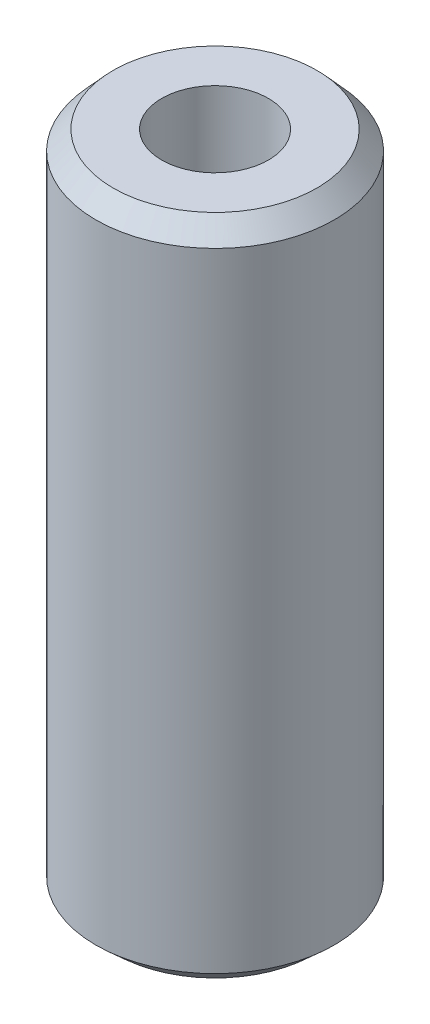
SolidWorks part; units mm, degrees
ref_plane "Front Plane" through (0, 0, 0) normal (0, 0, 1) x (1, 0, 0)
ref_plane "Top Plane" through (0, 0, 0) normal (0, 1, 0) x (1, 0, 0)
ref_plane "Right Plane" through (0, 0, 0) normal (1, 0, 0) x (0, 0, -1)
sketch "Sketch1" plane through (0, 0, 0) normal (0, 1, 0) x (1, 0, 0)
  circle A0 centre (0, 0) radius 10
  dimension "SHAFT_OD" = 20
extrude "Boss-Extrude1" add sketch "Sketch1" along normal blind 55.7509
sketch "Sketch2" plane through (0, 0, 0) normal (0, 1, 0) x (1, 0, 0)
  circle A0 centre (0, 0) radius 4.4831
  dimension "BORE_D" = 8.9661
extrude "Cut-Extrude1" cut sketch "Sketch2" along normal through all
chamfer "Chamfer1" distance 1.5942 angle 42.184 2 edges at (0, 55.7509, 10) (0, 0, 10) first distance on face at (0, 55.7509, 10) first distance on face at (0, 0, 4.4831)
